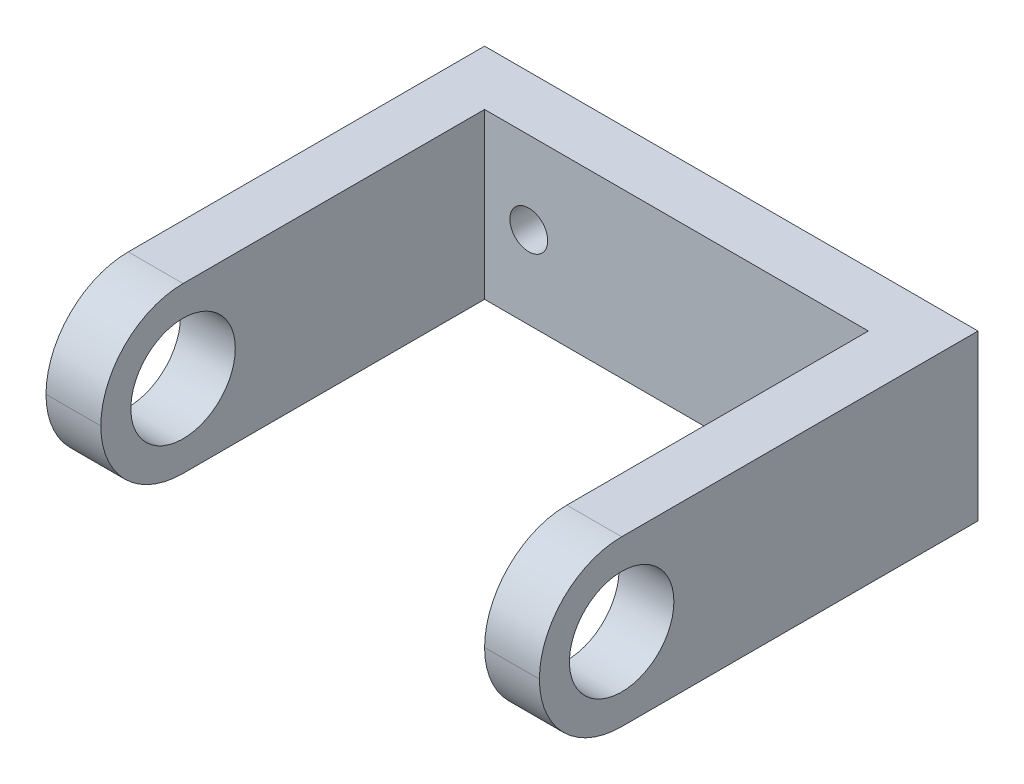
SolidWorks part; units mm, degrees
material "ABS"
ref_plane "Front Plane" through (0, 0, 0) normal (0, 0, 1) x (1, 0, 0)
ref_plane "Top Plane" through (0, 0, 0) normal (0, 1, 0) x (1, 0, 0)
ref_plane "Right Plane" through (0, 0, 0) normal (1, 0, 0) x (0, 0, -1)
sketch "Sketch1" plane through (0, 0, 0) normal (0, 1, 0) x (1, 0, 0)
  line L0 (-17.5, -7.5) -> (-22.5, -7.5)
  line L1 (-22.5, -7.5) -> (-22.5, 32.5)
  line L3 (-22.5, 32.5) -> (22.5, 32.5)
  line L5 (22.5, 32.5) -> (22.5, -7.5)
  line L6 (22.5, -7.5) -> (17.5, -7.5)
  line L7 (17.5, -7.5) -> (17.5, 27.5)
  line L9 (17.5, 27.5) -> (-17.5, 27.5)
  line L11 (-17.5, 27.5) -> (-17.5, -7.5)
  line L16 (0, 27.5) -> (0, 32.5) construction
  point P5 (0, 27.5)
  dimension "D1" = 5
  dimension "D2" = 35
  dimension "D3" = 27.5
  dimension "D6" = 7.5
extrude "Boss-Extrude1" add sketch "Sketch1" along normal mid plane 15
sketch "Sketch3" plane through (0, 0, 0) normal (1, 0, 0) x (0, 0, -1)
  circle A0 centre (0, 0) radius 4.7625
  dimension "D1" = 9.525
extrude "Cut-Extrude1" cut sketch "Sketch3" against normal through all both and the other way through all
fillet "Fillet1" radius 7.5 4 edges at (20, 7.5, 7.5) (20, -7.5, 7.5) (-20, -7.5, 7.5) (-20, 7.5, 7.5)
hole_wizard "#8-32 Tapped Hole1" positions "Sketch4" profile "Sketch5" tap size "#8-32" standard "ANSI Inch" end condition through all
sketch "Sketch4" plane through (0, 0, -27.5) normal (0, 0, 1) x (1, 0, 0)
  point P0 (-13.47, 0)
  point P3 (0, 0)
  point P4 (2.981, 0)
  dimension "D1" = 13.47
sketch "Sketch5" plane through (-13.47, 0, -27.5) normal (1, 0, 0) x (0, -1, 0)
  line L0 (0, 0) -> (0, 5)
  line L1 (0, 5) -> (1.7272, 5)
  line L2 (1.7272, 5) -> (1.7272, 0)
  line L5 (1.7272, 0) -> (0, 0)
  line L11 (0, -6.35) -> (0, 107.95) construction
  dimension "Thru Tap Drill Dia." = 3.4544
  dimension "Thru Tap Drill Depth" = 5
cosmetic thread "Hole Thread2" parameters "D2"=4.1656
